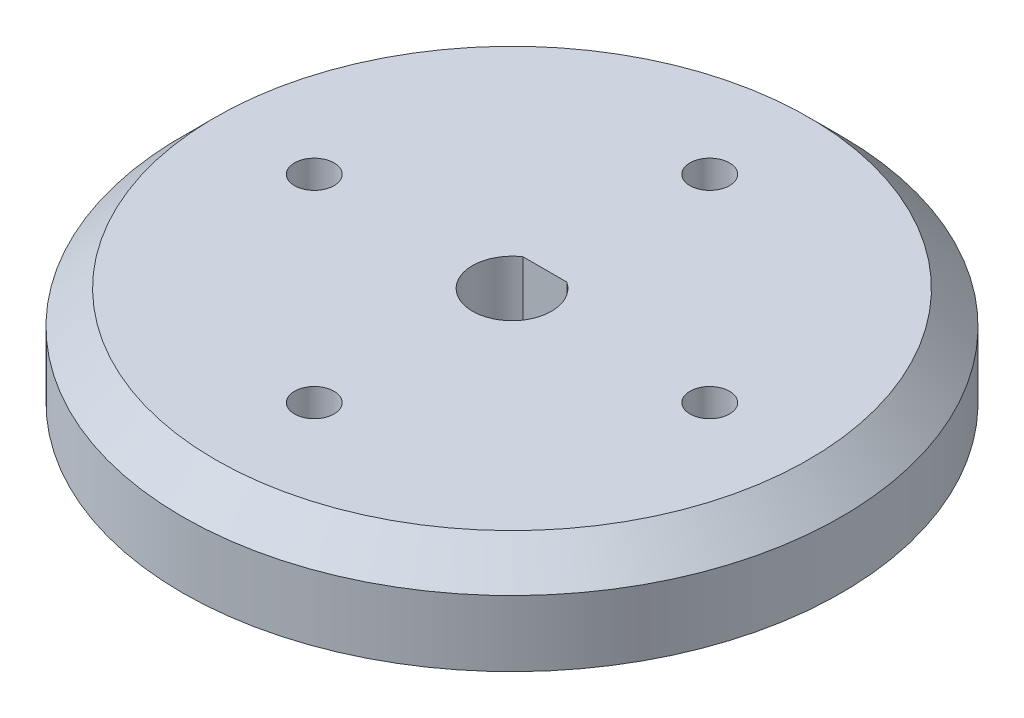
SolidWorks part; units mm, degrees
ref_plane "Front Plane" through (0, 0, 0) normal (0, 0, 1) x (1, 0, 0)
ref_plane "Top Plane" through (0, 0, 0) normal (0, 1, 0) x (1, 0, 0)
ref_plane "Right Plane" through (0, 0, 0) normal (1, 0, 0) x (0, 0, -1)
sketch "Sketch1" plane through (0, 0, 0) normal (0, 1, 0) x (1, 0, 0)
  line L0 (-1.6583, 2.5) -> (1.6583, 2.5)
  circle A0 centre (0, 0) radius 25
  circle A1 centre (0, 0) radius 15 construction
  circle A2 centre (0, 0) radius 3 construction
  circle A3 centre (0, 15) radius 1.5
  circle A4 centre (15, 0) radius 1.5
  circle A5 centre (0, -15) radius 1.5
  circle A6 centre (-15, 0) radius 1.5
  arc A7 (-1.6583, 2.5) -> (1.6583, 2.5) centre (0, 0) ccw
  point P16 (1.8425, 2.3675)
  dimension "D1" = 6
  dimension "D2" = 30
  dimension "D3" = 50
  dimension "D4" = 3
  dimension "D5" = 2.5
extrude "Boss-Extrude1" add sketch "Sketch1" along normal blind 7.5
chamfer "Chamfer1" distance 2.5 angle 45 1 edges at (0, 7.5, 25)
